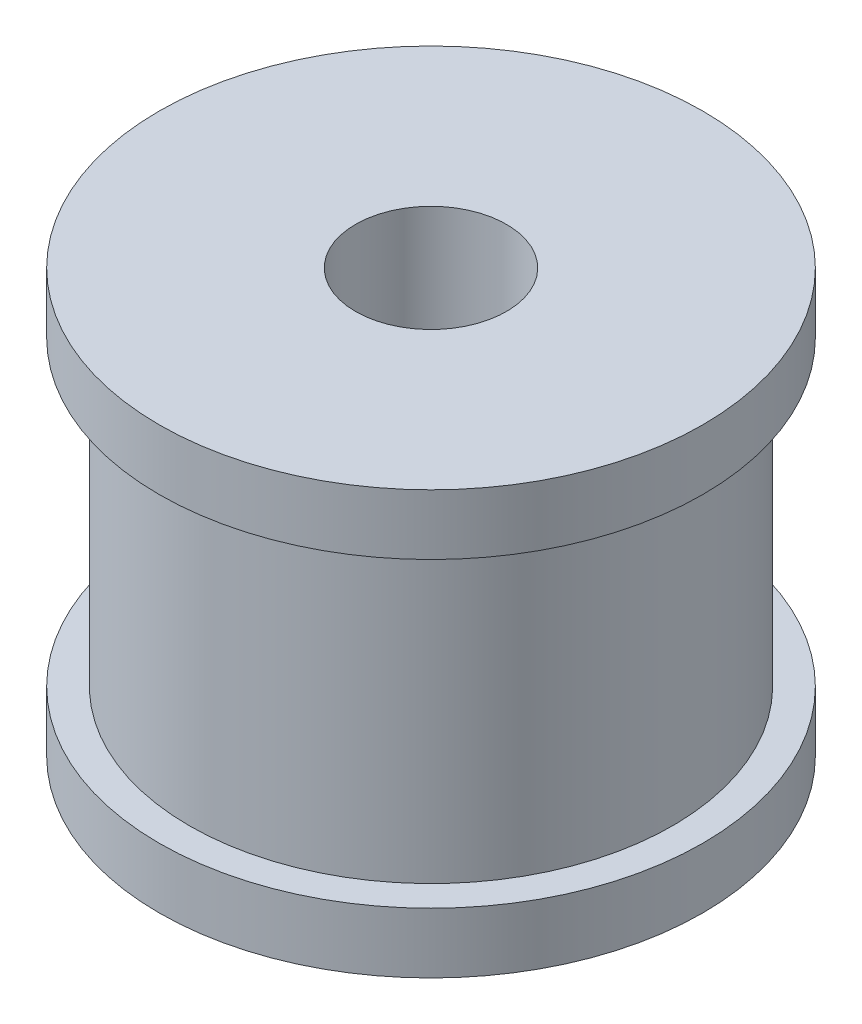
SolidWorks part; units mm, degrees
ref_plane "前视基准面" through (0, 0, 0) normal (0, 0, 1) x (1, 0, 0)
ref_plane "上视基准面" through (0, 0, 0) normal (0, 1, 0) x (1, 0, 0)
ref_plane "右视基准面" through (0, 0, 0) normal (1, 0, 0) x (0, 0, -1)
other "Configuration Table"
sketch "草图1" plane through (0, 0, 0) normal (0, 1, 0) x (1, 0, 0)
  circle A0 centre (0, 0) radius 2.5
  circle A1 centre (0, 0) radius 9
  circle A2 centre (0, 0) radius 8
  dimension "D1" = 5
  dimension "D2" = 18
  dimension "D3" = 16
extrude "凸台-拉伸1" add sketch "草图1" along normal blind 10 contours A2 A0 region at (-7.7737, 0, 0)
extrude "凸台-拉伸2" add sketch "草图1<3>" against normal blind 2 contours A1 A2 | A2 A0 region at (-8.7454, 0, 0) region at (-7.7737, 0, 0)
sketch "草图1<3>" plane through (0, 0, 0) normal (0, 1, 0) x (1, 0, 0) same geometry as "草图1"
extrude "凸台-拉伸3" add sketch "草图1<4>" along normal blind 2 from surface contours A1 A2 | A2 A0 region at (-8.7454, 0, 0) region at (-7.7737, 0, 0) starting at face at (0, 10, 2.5)
sketch "草图1<4>" plane through (0, 0, 0) normal (0, 1, 0) x (1, 0, 0) same geometry as "草图1"
